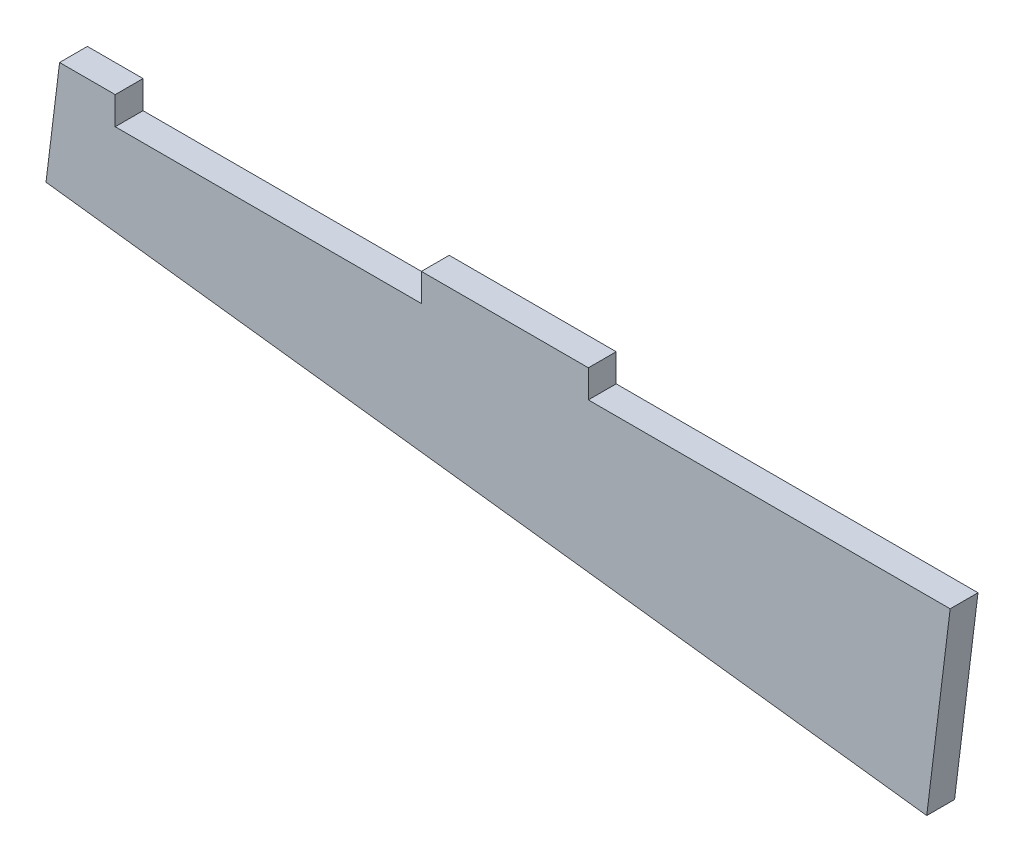
SolidWorks part; units mm, degrees
ref_plane "Front Plane" through (0, 0, 0) normal (0, 0, 1) x (1, 0, 0)
ref_plane "Top Plane" through (0, 0, 0) normal (0, 1, 0) x (1, 0, 0)
ref_plane "Right Plane" through (0, 0, 0) normal (1, 0, 0) x (0, 0, -1)
sketch "Sketch1" plane through (0, 0, 0) normal (0, 0, 1) x (1, 0, 0)
  line L0 (-195.3168, -62.6592) -> (-182.6168, -62.6592)
  line L4 (-182.6168, -62.6592) -> (-182.6168, -69.0092)
  line L5 (-182.6168, -69.0092) -> (-112.7668, -69.0092)
  line L6 (-112.7668, -69.0092) -> (-112.7668, -62.6592)
  line L7 (-112.7668, -62.6592) -> (-74.6668, -62.6592)
  line L8 (-74.6668, -62.6592) -> (-74.6668, -69.0092)
  line L9 (-74.6668, -69.0092) -> (7.8832, -69.0092)
  line L10 (7.8832, -69.0092) -> (2.5379, -112.5435)
  line L11 (2.5379, -112.5435) -> (-198.4122, -87.8699)
  line L12 (-198.4122, -87.8699) -> (-195.3168, -62.6592)
  line L13 (-378.8612, -54.018) -> (14.8388, -102.3583) construction
  dimension "D1" = 12.7
  dimension "D2" = 6.35
  dimension "D3" = 69.85
  dimension "D4" = 38.1
  dimension "D5" = 82.55
  dimension "D6" = 25.4
extrude "Boss-Extrude1" add sketch "Sketch1" against normal blind 6.35
